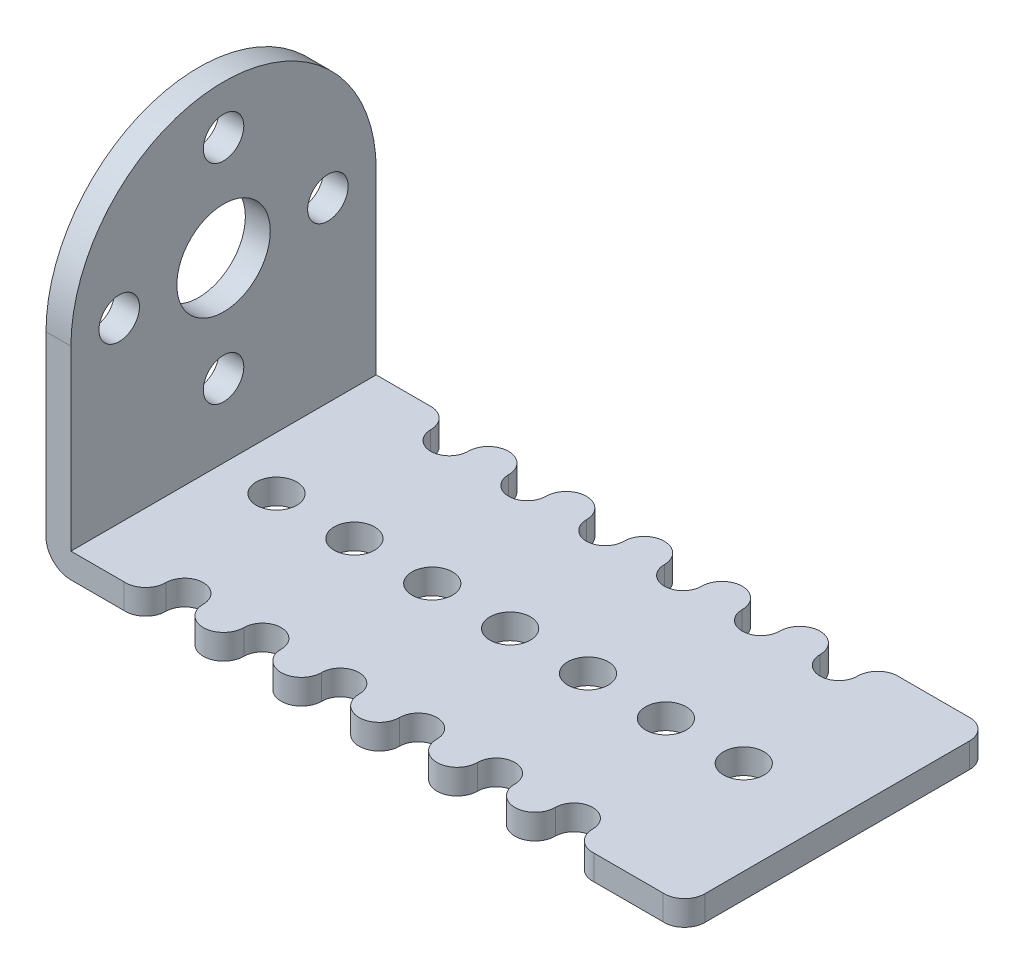
SolidWorks part; units mm, degrees
ref_plane "Front Plane" through (0, 0, 0) normal (0, 0, 1) x (1, 0, 0)
ref_plane "Top Plane" through (0, 0, 0) normal (0, 1, 0) x (1, 0, 0)
ref_plane "Right Plane" through (0, 0, 0) normal (1, 0, 0) x (0, 0, -1)
sketch "Sketch1" plane through (0, 0, 0) normal (0, 1, 0) x (1, 0, 0)
  line L0 (0, 12.446) -> (0, -12.446) construction
  line L1 (0, 12.446) -> (2.032, 12.446) construction
  line L2 (2.032, 12.446) -> (2.032, -12.446) construction
  line L3 (2.032, -12.446) -> (0, -12.446) construction
  line L4 (0, 0) -> (52.07, 0) construction
  line L5 (2.032, -12.446) -> (52.07, -12.446) construction
  line L6 (0, -10.795) -> (52.07, -10.795) construction
  line L7 (9.652, -10.795) -> (9.652, -12.446) construction
  line L8 (16.002, -12.446) -> (16.002, -10.795) construction
  line L9 (22.352, -12.446) -> (22.352, -10.795) construction
  line L10 (28.702, -12.446) -> (28.702, -10.795) construction
  line L11 (35.052, -12.446) -> (35.052, -10.795) construction
  line L12 (41.402, -12.446) -> (41.402, -10.795) construction
  line L13 (42.926, -10.795) -> (44.704, -10.795) construction
  line L14 (42.926, -10.795) -> (42.926, -12.446) construction
  line L15 (42.926, -12.446) -> (44.704, -12.446) construction
  line L16 (2.032, -12.446) -> (6.35, -12.446)
  line L17 (2.032, 12.446) -> (2.032, -12.446)
  line L18 (52.07, -12.446) -> (52.07, -10.795) construction
  line L19 (52.07, -10.795) -> (52.07, 0) construction
  line L20 (44.704, -12.446) -> (50.292, -12.446)
  line L21 (52.07, -10.795) -> (52.07, 10.795)
  line L22 (52.07, 12.446) -> (52.07, 10.795) construction
  line L23 (42.926, 12.446) -> (44.704, 12.446) construction
  line L24 (42.926, 10.795) -> (42.926, 12.446) construction
  line L25 (42.926, 10.795) -> (44.704, 10.795) construction
  line L26 (41.402, 12.446) -> (41.402, 10.795) construction
  line L27 (35.052, 12.446) -> (35.052, 10.795) construction
  line L28 (28.702, 12.446) -> (28.702, 10.795) construction
  line L29 (22.352, 12.446) -> (22.352, 10.795) construction
  line L30 (16.002, 12.446) -> (16.002, 10.795) construction
  line L31 (9.652, 10.795) -> (9.652, 12.446) construction
  line L32 (44.704, 12.446) -> (50.292, 12.446)
  line L33 (2.032, 12.446) -> (6.35, 12.446)
  circle A0 centre (9.652, -10.795) radius 1.524 construction
  circle A1 centre (16.002, -10.795) radius 1.524 construction
  circle A2 centre (22.352, -10.795) radius 1.524 construction
  circle A3 centre (28.702, -10.795) radius 1.524 construction
  circle A4 centre (35.052, -10.795) radius 1.524 construction
  circle A5 centre (41.402, -10.795) radius 1.524 construction
  arc A6 (8.128, -10.795) -> (11.176, -10.795) centre (9.652, -10.795) cw
  arc A7 (14.478, -10.795) -> (17.526, -10.795) centre (16.002, -10.795) cw
  arc A8 (20.828, -10.795) -> (23.876, -10.795) centre (22.352, -10.795) cw
  arc A9 (27.178, -10.795) -> (30.226, -10.795) centre (28.702, -10.795) cw
  arc A10 (33.528, -10.795) -> (36.576, -10.795) centre (35.052, -10.795) cw
  arc A11 (39.878, -10.795) -> (42.926, -10.795) centre (41.402, -10.795) cw
  arc A12 (11.176, -10.795) -> (14.478, -10.795) centre (12.827, -10.795) ccw
  arc A13 (17.526, -10.795) -> (20.828, -10.795) centre (19.177, -10.795) ccw
  arc A14 (23.876, -10.795) -> (27.178, -10.795) centre (25.527, -10.795) ccw
  arc A15 (30.226, -10.795) -> (33.528, -10.795) centre (31.877, -10.795) ccw
  arc A16 (36.576, -10.795) -> (39.878, -10.795) centre (38.227, -10.795) ccw
  arc A17 (42.926, -10.795) -> (44.704, -12.446) centre (44.5815, -10.795) ccw
  circle A18 centre (6.35, 0) radius 1.651
  circle A19 centre (12.7, 0) radius 1.651
  circle A20 centre (19.05, 0) radius 1.651
  circle A21 centre (25.4, 0) radius 1.651
  circle A22 centre (31.75, 0) radius 1.651
  circle A23 centre (38.1, 0) radius 1.651
  circle A24 centre (44.45, 0) radius 1.651
  arc A25 (8.128, -10.795) -> (6.35, -12.446) centre (6.4725, -10.795) cw
  arc A26 (52.07, -10.795) -> (50.292, -12.446) centre (50.4145, -10.795) cw
  circle A27 centre (41.402, 10.795) radius 1.524 construction
  circle A28 centre (35.052, 10.795) radius 1.524 construction
  circle A29 centre (28.702, 10.795) radius 1.524 construction
  circle A30 centre (22.352, 10.795) radius 1.524 construction
  circle A31 centre (16.002, 10.795) radius 1.524 construction
  circle A32 centre (9.652, 10.795) radius 1.524 construction
  arc A33 (52.07, 10.795) -> (50.292, 12.446) centre (50.4145, 10.795) ccw
  arc A34 (42.926, 10.795) -> (44.704, 12.446) centre (44.5815, 10.795) cw
  arc A35 (36.576, 10.795) -> (39.878, 10.795) centre (38.227, 10.795) cw
  arc A36 (30.226, 10.795) -> (33.528, 10.795) centre (31.877, 10.795) cw
  arc A37 (23.876, 10.795) -> (27.178, 10.795) centre (25.527, 10.795) cw
  arc A38 (17.526, 10.795) -> (20.828, 10.795) centre (19.177, 10.795) cw
  arc A39 (11.176, 10.795) -> (14.478, 10.795) centre (12.827, 10.795) cw
  arc A40 (39.878, 10.795) -> (42.926, 10.795) centre (41.402, 10.795) ccw
  arc A41 (33.528, 10.795) -> (36.576, 10.795) centre (35.052, 10.795) ccw
  arc A42 (27.178, 10.795) -> (30.226, 10.795) centre (28.702, 10.795) ccw
  arc A43 (20.828, 10.795) -> (23.876, 10.795) centre (22.352, 10.795) ccw
  arc A44 (14.478, 10.795) -> (17.526, 10.795) centre (16.002, 10.795) ccw
  arc A45 (8.128, 10.795) -> (11.176, 10.795) centre (9.652, 10.795) ccw
  arc A46 (8.128, 10.795) -> (6.35, 12.446) centre (6.4725, 10.795) ccw
  point P7 (9.652, -12.446)
  point P9 (16.002, -12.446)
  point P11 (22.352, -12.446)
  point P12 (28.702, -12.446)
  point P13 (35.052, -12.446)
  point P14 (41.402, -12.446)
  point P21 (16.002, -12.446)
  point P120 (2.032, 0)
  dimension "D11" = 3.048
  dimension "D12" = 3.048
  dimension "D14" = 3.048
  dimension "D15" = 3.048
  dimension "D16" = 3.048
  dimension "D17" = 3.048
  dimension "D18" = 1.778
  dimension "D20" = 3.302
  dimension "D21" = 3.302
  dimension "D22" = 3.302
  dimension "D23" = 3.302
  dimension "D24" = 3.302
  dimension "D25" = 3.302
  dimension "D26" = 3.302
  dimension "D1" = 24.892
  dimension "D2" = 2.032
  dimension "D3" = 52.07
  dimension "D4" = 9.652
  dimension "D5" = 6.35
  dimension "D6" = 6.35
  dimension "D7" = 6.35
  dimension "D8" = 6.35
  dimension "D9" = 6.35
  dimension "D10" = 10.795
  dimension "D13" = 1.651
  dimension "D19" = 6.35
  dimension "D27" = 6.35
  dimension "D28" = 6.35
  dimension "D29" = 6.35
  dimension "D30" = 6.35
  dimension "D31" = 6.35
  dimension "D32" = 6.35
  dimension "D33" = 1.778
  dimension "D34" = 1.778
extrude "Boss-Extrude1" add sketch "Sketch1" along normal blind 2.032
sketch "Sketch2" plane through (0, 0, 0) normal (1, 0, 0) x (0, 0, -1)
  line L0 (-12.446, 2.032) -> (-12.446, 0) construction
  line L1 (12.446, 2.032) -> (-12.446, 2.032)
  line L2 (12.446, 2.032) -> (12.446, 16.51)
  line L3 (12.446, 16.51) -> (-12.446, 16.51) construction
  line L4 (-12.446, 2.032) -> (-12.446, 16.51)
  line L5 (0, 16.51) -> (0, 8.001) construction
  circle A0 centre (0, 8.001) radius 1.651
  circle A1 centre (-8.509, 16.51) radius 1.651
  circle A2 centre (0, 25.019) radius 1.651
  circle A3 centre (8.509, 16.51) radius 1.651
  arc A4 (12.446, 16.51) -> (-12.446, 16.51) centre (0, 16.51) ccw
  circle A5 centre (0, 16.51) radius 3.81
  point P20 (0, 16.51)
  dimension "D3" = 3.302
  dimension "D5" = 3.302
  dimension "D9" = 7.62
  dimension "D1" = 14.478
  dimension "D2" = 8.509
  dimension "D6" = 8.509
  dimension "D7" = 8.509
  dimension "D8" = 8.509
  dimension "D4" = 4
extrude "Boss-Extrude2" add sketch "Sketch2" along normal blind 2.032 separate body
sketch "Sketch3" plane through (0, 0, 12.446) normal (0, 0, 1) x (1, 0, 0)
  line L0 (2.032, 2.032) -> (0, 2.032) construction
  line L1 (2.032, 2.032) -> (2.032, 0) construction
  line L2 (0, 2.032) -> (2.032, 2.032)
  line L3 (2.032, 2.032) -> (2.032, 0)
  arc A0 (0, 2.032) -> (2.032, 0) centre (2.032, 2.032) ccw
  dimension "D1" = 2.032
extrude "Boss-Extrude3" add sketch "Sketch3" against normal up to surface (24.892 mm away) up to face at (4.191, 1.016, -12.446)
equation "\"D6@Sketch1\"=\"D5@Sketch1\""
equation "\"D7@Sketch1\"=\"D5@Sketch1\""
equation "\"D8@Sketch1\"=\"D5@Sketch1\""
equation "\"D9@Sketch1\"=\"D5@Sketch1\""
equation "\"D12@Sketch1\"=\"D11@Sketch1\""
equation "\"D14@Sketch1\"=\"D11@Sketch1\""
equation "\"D15@Sketch1\"=\"D11@Sketch1\""
equation "\"D16@Sketch1\"=\"D11@Sketch1\""
equation "\"D17@Sketch1\"=\"D11@Sketch1\""
equation "\"D21@Sketch1\"=\"D20@Sketch1\""
equation "\"D22@Sketch1\"=\"D20@Sketch1\""
equation "\"D23@Sketch1\"=\"D20@Sketch1\""
equation "\"D24@Sketch1\"=\"D20@Sketch1\""
equation "\"D25@Sketch1\"=\"D20@Sketch1\""
equation "\"D26@Sketch1\"=\"D20@Sketch1\""
equation "\"D28@Sketch1\"=\"D27@Sketch1\""
equation "\"D29@Sketch1\"=\"D27@Sketch1\""
equation "\"D30@Sketch1\"=\"D27@Sketch1\""
equation "\"D31@Sketch1\"=\"D27@Sketch1\""
equation "\"D32@Sketch1\"=\"D27@Sketch1\""
equation "\"D6@Sketch2\"=\"D2@Sketch2\""
equation "\"D7@Sketch2\"=\"D2@Sketch2\""
